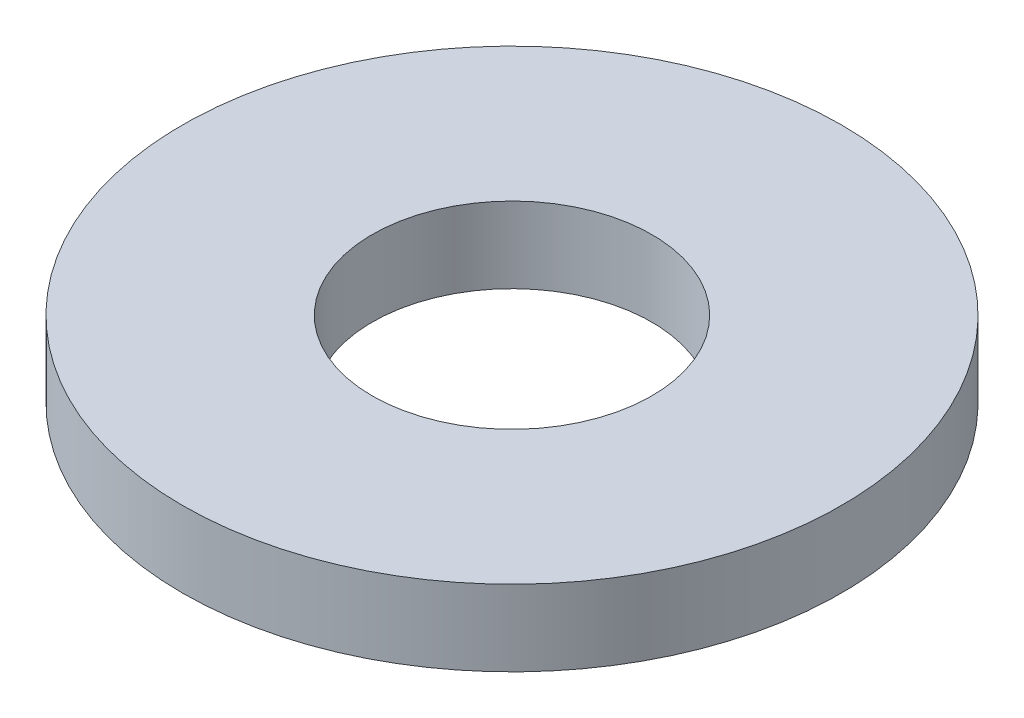
SolidWorks part; units mm, degrees
ref_plane "Front Plane" through (0, 0, 0) normal (0, 0, 1) x (1, 0, 0)
ref_plane "Top Plane" through (0, 0, 0) normal (0, 1, 0) x (1, 0, 0)
ref_plane "Right Plane" through (0, 0, 0) normal (1, 0, 0) x (0, 0, -1)
sketch "Sketch1" plane through (0, 0, 0) normal (0, 1, 0) x (1, 0, 0)
  circle A0 centre (0, 0) radius 82.5
  dimension "FLANGE_OD" = 165
extrude "Boss-Extrude1" add sketch "Sketch1" along normal blind 19
sketch "Sketch2" plane through (0, 0, 0) normal (0, 1, 0) x (1, 0, 0)
  circle A0 centre (0, 0) radius 35
  dimension "BORE_D" = 70
extrude "Cut-Extrude1" cut sketch "Sketch2" along normal through all
sketch "Sketch3" plane through (0, 19, 0) normal (0, 1, 0) x (1, 0, 0)
  circle A0 centre (0, 0) radius 28.7195 construction
  circle A1 centre (-28.7195, 0) radius 4.5506
  dimension "BOLT_D" = 9.1013
  dimension "BOLT_PCD" = 57.439
extrude "Cut-Extrude2" cut sketch "Sketch3" against normal blind 15.0547 rebuild error yes
pattern_circular "CirPattern1" count 5 over 360 rebuild error yes
